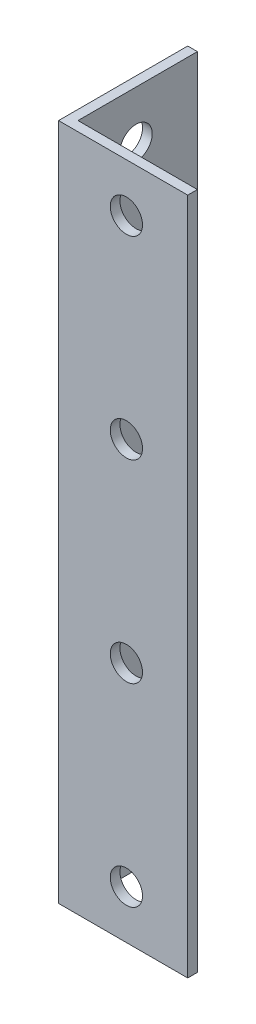
SolidWorks part; units mm, degrees
ref_plane "Спереди" through (0, 0, 0) normal (0, 0, 1) x (1, 0, 0)
ref_plane "Сверху" through (0, 0, 0) normal (0, 1, 0) x (1, 0, 0)
ref_plane "Справа" through (0, 0, 0) normal (1, 0, 0) x (0, 0, -1)
sketch "Эскиз1" plane through (0, 0, 0) normal (0, 1, 0) x (1, 0, 0)
  line L0 (0, 40) -> (0, 0)
  line L1 (0, 0) -> (40, 0)
  dimension "D1" = 40
extrude "Вытянуть-Тонкостенный1" add sketch "Эскиз1" along normal blind 210 thin thin type one direction reverse wall 3
sketch "Эскиз2" plane through (0, 0, 0) normal (-1, 0, 0) x (0, 0, 1)
  circle A0 centre (-21, 15) radius 5
  circle A1 centre (-21, 75) radius 5
  circle A6 centre (-21, 135) radius 5
  circle A7 centre (-21, 195) radius 5
  point P6 (0, 0)
  dimension "D1" = 4
extrude "Вырез-Вытянуть1" cut sketch "Эскиз2" against normal through all
sketch "Эскиз3" plane through (0, 0, 0) normal (0, 0, 1) x (1, 0, 0)
  circle A0 centre (21, 15) radius 5
  circle A1 centre (21, 75) radius 5
  circle A4 centre (21, 135) radius 5
  circle A5 centre (21, 195) radius 5
  dimension "D1" = 4
extrude "Вырез-Вытянуть2" cut sketch "Эскиз3" against normal through all
